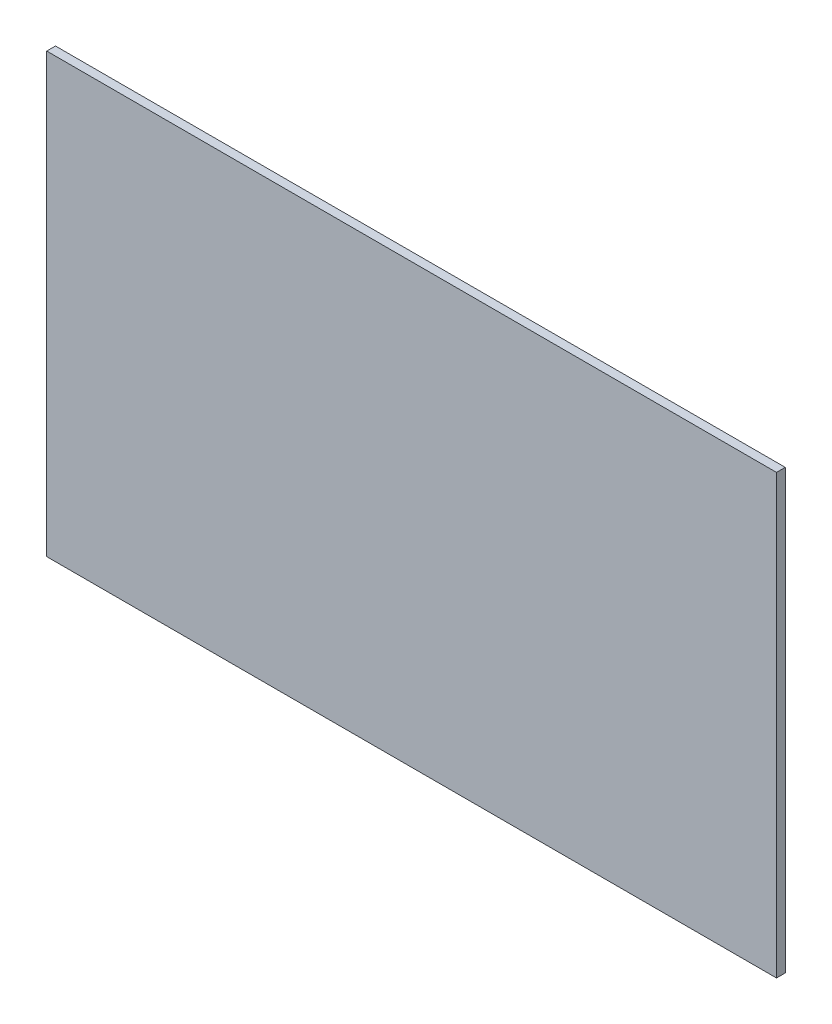
SolidWorks part; units mm, degrees
ref_plane "Front Plane" through (0, 0, 0) normal (0, 0, 1) x (1, 0, 0)
ref_plane "Top Plane" through (0, 0, 0) normal (0, 1, 0) x (1, 0, 0)
ref_plane "Right Plane" through (0, 0, 0) normal (1, 0, 0) x (0, 0, -1)
sketch "Sketch1" plane through (0, 0, 0) normal (0, 0, 1) x (1, 0, 0)
  line L1 (-125, 75) -> (125, 75)
  line L2 (-125, 75) -> (-125, -75)
  line L3 (-125, -75) -> (125, -75)
  line L4 (125, 75) -> (125, -75)
  line L5 (-125, 75) -> (125, -75) construction
  line L6 (-125, -75) -> (125, 75) construction
  point P0 (0, 0)
  dimension "D1" = 150
  dimension "D2" = 250
extrude "Boss-Extrude1" add sketch "Sketch1" along normal blind 3
